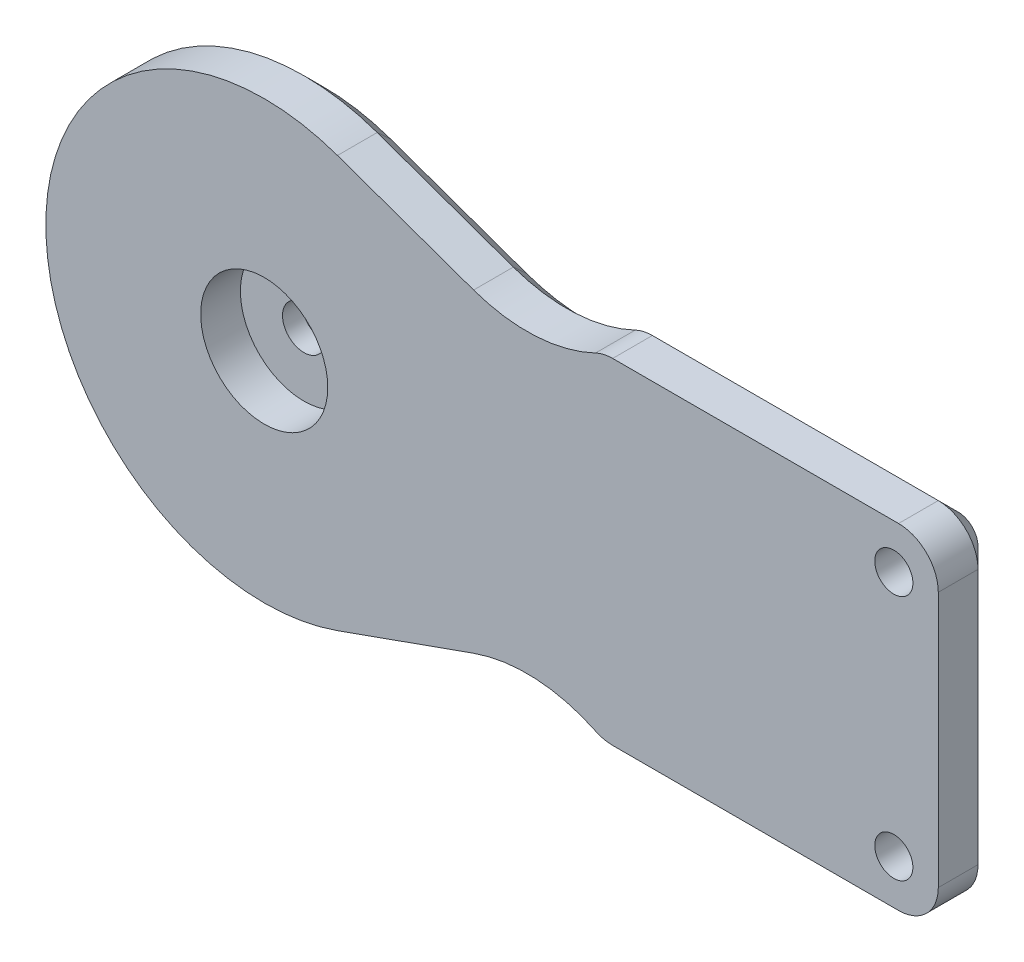
SolidWorks part; units mm, degrees
material "ABS"
ref_plane "Front Plane" through (0, 0, 0) normal (0, 0, 1) x (1, 0, 0)
ref_plane "Top Plane" through (0, 0, 0) normal (0, 1, 0) x (1, 0, 0)
ref_plane "Right Plane" through (0, 0, 0) normal (1, 0, 0) x (0, 0, -1)
sketch "Sketch1" plane through (0, 0, 0) normal (0, 0, 1) x (1, 0, 0)
  line L0 (42.6696, 14) -> (42.6696, 21.1)
  line L1 (23.6696, -14) -> (42.6696, -14) construction
  line L3 (23.6696, 14) -> (42.6696, 14) construction
  line L5 (9.2232, 25.9072) -> (42.6696, 14)
  line L6 (42.6696, -14) -> (9.2232, -25.9072)
  line L7 (42.6696, -21.1) -> (84.8696, -21.1)
  line L8 (42.6696, -21.1) -> (42.6696, -14)
  line L9 (42.6696, 21.1) -> (84.8696, 21.1)
  line L10 (84.8696, -21.1) -> (84.8696, 21.1)
  line L11 (42.6696, -21.1) -> (84.8696, 21.1) construction
  line L12 (42.6696, 21.1) -> (84.8696, -21.1) construction
  line L13 (48.2696, -15.5) -> (79.2696, -15.5) construction
  line L14 (48.2696, -15.5) -> (48.2696, 15.5) construction
  line L15 (48.2696, 15.5) -> (79.2696, 15.5) construction
  line L16 (79.2696, -15.5) -> (79.2696, 15.5) construction
  line L17 (48.2696, -15.5) -> (79.2696, 15.5) construction
  line L18 (48.2696, 15.5) -> (79.2696, -15.5) construction
  line L19 (23.6696, 14) -> (8.5248, 26.1453) construction
  line L20 (23.6696, -14) -> (9.2232, -25.9072) construction
  arc A0 (9.2232, 25.9072) -> (9.2232, -25.9072) centre (0, 0) ccw
  circle A4 centre (79.2696, 15.5) radius 1.5
  circle A5 centre (79.2696, -15.5) radius 1.5
  circle A7 centre (0, 0) radius 2.7
  point P3 (27.5, 0)
  point P8 (63.7696, 0)
  point P18 (63.7696, 0)
  dimension "D8" = 27.5
  dimension "D3" = 5.4
  dimension "D1" = 28
  dimension "D2" = 42.2
  dimension "D4" = 19
  dimension "D5" = 42.2
  dimension "D6" = 31
extrude "Boss-Extrude1" add sketch "Sketch1" along normal blind 7.5
ref_plane "Plane1" through (0, 0, 7.5) normal (0, 0, 1) x (1, 0, 0)
sketch "Sketch3" plane through (0, 0, 7.5) normal (0, 0, 1) x (1, 0, 0)
  circle A0 centre (0, 0) radius 8
  dimension "D1" = 16
extrude "Cut-Extrude2" cut sketch "Sketch3" against normal blind 5
fillet "Fillet2" radius 20 2 edges at (42.6696, -14, 3.75) (42.6696, 14, 3.75)
sketch "Sketch5" plane through (0, 0, 7.5) normal (0, 0, 1) x (1, 0, 0)
  point P0 (79.2696, -15.5)
  point P3 (79.2696, 15.5)
  point P12 (79.2696, 15.5)
  point P15 (79.2696, -15.5)
  point P22 (79.2696, 15.5)
  point P24 (79.2696, -15.5)
hole_wizard "Taladro de margen para M41" positions "Sketch5" profile "Sketch6" hole size "M4" standard "Ansi Metric" end condition through all
sketch "Sketch6" plane through (79.2696, -15.5, 7.5) normal (1, 0, 0) x (0, -1, 0)
  line L0 (0, 0) -> (0, 7.5)
  line L1 (0, 7.5) -> (2.4, 7.5)
  line L2 (2.4, 7.5) -> (2.4, 0)
  line L5 (2.4, 0) -> (0, 0)
  line L11 (0, -6.35) -> (0, 107.95) construction
  dimension "Diámetro de taladro hasta el siguiente" = 4.8
  dimension "Profundidad de taladro hasta el siguiente" = 7.5
fillet "Fillet3" radius 5 4 edges at (84.8696, -21.1, 3.75) (84.8696, 21.1, 3.75) (42.6696, -21.1, 3.75) (42.6696, 21.1, 3.75)
chamfer "Chamfer1" distance 2.5 angle 45 12 edges at (84.8696, 0, 0) (83.4051, 19.6355, 0) (83.4051, -19.6355, 0) (61.871, 21.1, 0) (61.871, -21.1, 0) (-27.5, 0, 0) (34.1185, 18.6739, 0) (34.1185, -18.6739, 0) (17.7936, 22.8561, 0) (17.7936, -22.8561, 0) (42.7648, 20.9758, 0) (42.7648, -20.9758, 0)
sketch "Sketch7" plane through (0, 0, 0) normal (0, 0, -1) x (-1, 0, 0)
  line L0 (-5.445, 4.565) -> (5.445, 4.565)
  line L1 (-4.245, -3.365) -> (4.245, -3.365)
  line L2 (-4.245, -3.365) -> (-4.245, 3.365)
  line L3 (-4.245, 3.365) -> (4.245, 3.365)
  line L4 (4.245, -3.365) -> (4.245, 3.365)
  line L5 (-4.245, -3.365) -> (4.245, 3.365) construction
  line L6 (-4.245, 3.365) -> (4.245, -3.365) construction
  line L7 (5.445, -4.565) -> (5.445, 4.565)
  line L8 (-5.445, -4.565) -> (5.445, -4.565)
  line L9 (-5.445, -4.565) -> (-5.445, 4.565)
  point P0 (0, 0)
  dimension "D1" = 8.49
  dimension "D2" = 6.73
  dimension "D3" = 1.2
extrude "Boss-Extrude2" add sketch "Sketch7" along normal blind 15
fillet "Fillet5" radius 2.5 4 edges at (5.445, 4.565, -7.5) (-5.445, 4.565, -7.5) (5.445, -4.565, -7.5) (-5.445, -4.565, -7.5)
